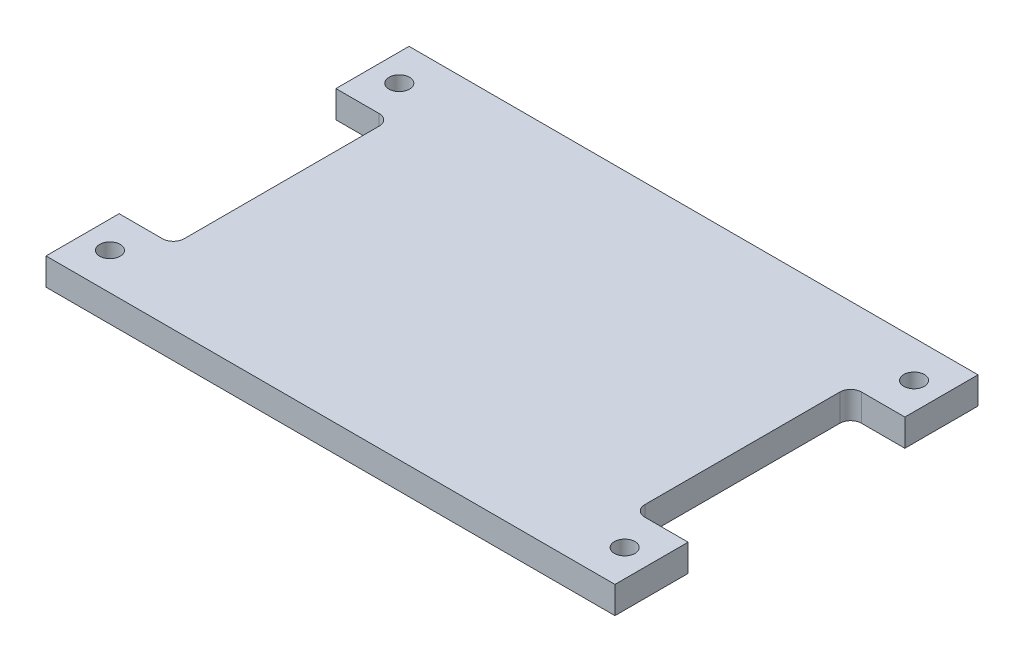
SolidWorks part; units mm, degrees
material "1060 Alloy"
ref_plane "Front Plane" through (0, 0, 0) normal (0, 0, 1) x (1, 0, 0)
ref_plane "Top Plane" through (0, 0, 0) normal (0, 1, 0) x (1, 0, 0)
ref_plane "Right Plane" through (0, 0, 0) normal (1, 0, 0) x (0, 0, -1)
sketch "Sketch1" plane through (0, 0, 0) normal (0, 1, 0) x (1, 0, 0)
  line L1 (-45.1884, 47.6545) -> (88.1616, 47.6545)
  line L2 (-45.1884, 47.6545) -> (-45.1884, -37.4355)
  line L3 (-45.1884, -37.4355) -> (88.1616, -37.4355)
  line L4 (88.1616, 47.6545) -> (88.1616, -37.4355)
  dimension "D1" = 133.35
  dimension "D2" = 85.09
extrude "Boss-Extrude1" add sketch "Sketch1" along normal blind 6.35
sketch "Sketch4" plane through (0, 6.35, 0) normal (0, 1, 0) x (1, 0, 0)
  line L0 (88.1616, -37.4355) -> (88.1616, 47.6545) construction
  line L1 (88.1616, 30.5095) -> (75.4616, 30.5095)
  line L2 (88.1616, 30.5095) -> (88.1616, -20.2905)
  line L3 (88.1616, -20.2905) -> (75.4616, -20.2905)
  line L4 (75.4616, 30.5095) -> (75.4616, -20.2905)
  line L5 (21.4866, 47.6545) -> (21.4866, -37.4355) construction
  line L6 (88.1616, 47.6545) -> (-45.1884, 47.6545) construction
  line L7 (-45.1884, -37.4355) -> (88.1616, -37.4355) construction
  line L12 (-45.1884, 5.1095) -> (88.1616, 5.1095) construction
  line L13 (-45.1884, 30.5095) -> (-45.1884, -20.2905)
  line L14 (-45.1884, 30.5095) -> (-32.4884, 30.5095)
  line L15 (-45.1884, -20.2905) -> (-32.4884, -20.2905)
  line L16 (-32.4884, 30.5095) -> (-32.4884, -20.2905)
  line L17 (-45.1884, 47.6545) -> (-45.1884, -37.4355) construction
  dimension "D1" = 12.7
  dimension "D2" = 50.8
  dimension "D3" = 12.7
  dimension "D4" = 50.8
extrude "Cut-Extrude8" cut sketch "Sketch4" against normal through all
sketch "Sketch2" plane through (0, 6.35, 0) normal (0, 1, 0) x (1, 0, 0)
  line L0 (88.1616, -37.4355) -> (88.1616, -20.2905) construction
  line L1 (-45.1884, -37.4355) -> (88.1616, -37.4355) construction
  line L2 (21.4866, 47.6545) -> (21.4866, -37.4355) construction
  line L3 (88.1616, 47.6545) -> (-45.1884, 47.6545) construction
  circle A0 centre (81.8116, -28.7995) radius 2.413
  circle A1 centre (81.8116, 39.0185) radius 2.413
  circle A4 centre (-38.8384, 39.0185) radius 2.413
  circle A5 centre (-38.8384, -28.7995) radius 2.413
  point P0 (81.8116, -28.7995)
  point P2 (81.8116, 39.0185)
  point P20 (-38.8384, 39.0185)
  point P21 (-38.8384, -28.7995)
  dimension "D5" = 4.826
  dimension "D1" = 6.35
  dimension "D3" = 8.636
  dimension "D4" = 8.636
extrude "Cut-Extrude1" cut sketch "Sketch2" against normal through all
fillet "Fillet1" radius 2.54 4 edges at (75.4616, 3.175, -30.5095) (75.4616, 3.175, 20.2905) (-32.4884, 3.175, 20.2905) (-32.4884, 3.175, -30.5095)
